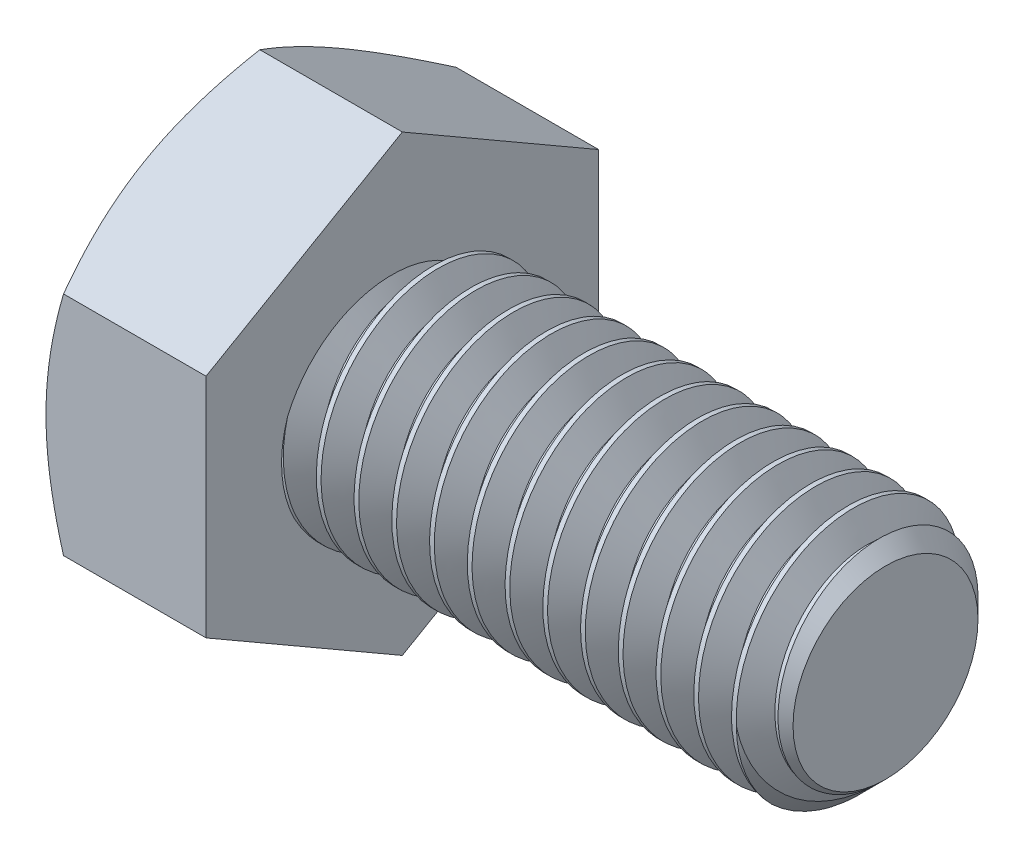
SolidWorks part; units mm, degrees
ref_plane "Front Plane" through (0, 0, 0) normal (0, 0, 1) x (1, 0, 0)
ref_plane "Top Plane" through (0, 0, 0) normal (0, 1, 0) x (1, 0, 0)
ref_plane "Right Plane" through (0, 0, 0) normal (1, 0, 0) x (0, 0, -1)
sketch "Sketch1" plane through (0, 0, 0) normal (0, 0, 1) x (1, 0, 0)
  line L0 (-10.65, 0) -> (10.65, 0) construction
  line L1 (-5.35, 6.5) -> (-5.35, -6.5) construction
  line L2 (-10.65, 6.5) -> (-10.65, -6.5) construction
  line L3 (10.65, 4) -> (10.65, -4) construction
  point P8 (6.275, -4)
  dimension "D1" = 4.375
  dimension "Thread Dia" = 8
  dimension "Hex" = 13
  dimension "Head Ht" = 5.3
  dimension "Length" = 16
ref_plane "Plane2" through (10.65, 0, 0) normal (1, 0, 0) x (0, 0, -1)
sketch "Sketch2" plane through (10.65, 0, 0) normal (1, 0, 0) x (0, 0, -1)
  circle A0 centre (0, 0) radius 4
extrude "Boss-Extrude1" add sketch "Sketch2" against normal up to vertex (16 mm away) up to point (-5.35, -6.5, 0)
sketch "Sketch4" plane through (10.65, 0, 0) normal (1, 0, 0) x (0, 0, -1)
  circle A1 centre (0, 0) radius 4
  circle A2 centre (0, 0) radius 4
  dimension "D1" = 0
curve "Helix/Spiral1" pitch 1.25 height 17.25 turns 13.8 parameters "Pitch"=1.25
chamfer "Chamfer1" distance 0.9375 angle 45 1 edges at (10.65, 0, -4)
sketch "Sketch5" plane through (0, 0, 0) normal (0, 0, 1) x (1, 0, 0)
  line L0 (10.65, 4) -> (11.1187, 3.1881)
  line L1 (11.1187, 3.1881) -> (11.275, 3.1881)
  line L2 (11.275, 3.1881) -> (11.7437, 4)
  line L3 (10.65, 4) -> (11.7437, 4)
  line L4 (11.1969, 3.1881) -> (11.1969, 4) construction
  line L5 (10.8844, 3.5941) -> (11.5094, 3.5941) construction
  line L6 (10.65, -4) -> (10.65, 4) construction
  dimension "D1" = 60
  dimension "D2" = 0.1562
  dimension "D3" = 0.625
sweep "Cut-Sweep1" cut profiles "Sketch5" path "Helix/Spiral1" align with end faces yes
sketch "Sketch3" plane through (-5.35, 0, 0) normal (-1, 0, 0) x (0, 0, 1)
  line L0 (0, 6.5) -> (0, -6.5) construction
  line L1 (-6.5, -3.7528) -> (0, -7.5056)
  line L2 (0, -7.5056) -> (6.5, -3.7528)
  line L3 (6.5, -3.7528) -> (6.5, 3.7528)
  line L4 (6.5, 3.7528) -> (0, 7.5056)
  line L5 (0, 7.5056) -> (-6.5, 3.7528)
  line L6 (-6.5, 3.7528) -> (-6.5, -3.7528)
  circle A0 centre (0, 0) radius 6.5 construction
extrude "Boss-Extrude2" add sketch "Sketch3" along normal up to vertex (5.3 mm away) up to point (-10.65, -6.5, 0)
sketch "Sketch6" plane through (-10.65, 0, 0) normal (-1, 0, 0) x (0, 0, 1)
  circle A0 centre (0, 0) radius 6.5 construction
  circle A1 centre (0, 0) radius 6.5
extrude "Cut-Extrude1" cut sketch "Sketch6" against normal through all draft 60 flip side to cut
sketch "Sketch7" plane through (-10.65, 0, 0) normal (-1, 0, 0) x (0, 0, 1)
  line L0 (0, 0) -> (0, 6.5) construction
  line L2 (0, 6.5) -> (0, -6.5) construction
  line L3 (-5.6292, 3.25) -> (5.6292, 3.25) construction
  circle A1 centre (0, 0) radius 6.5 construction
  text T0 "8.8\r\n" font "Arial" height in points 6
  point P8 (0, 3.25)
extrude "Cut-Extrude2" cut sketch "Sketch7" against normal blind 0.25
sketch "Sketch9" plane through (0, 0, 0) normal (0, 0, 1) x (1, 0, 0)
  line L0 (-5.35, 4) -> (-5.35, 0)
  line L1 (-5.35, 0) -> (-39.35, 0)
  line L2 (-39.35, 0) -> (-43.35, 4)
  line L3 (-43.35, 4) -> (-5.35, 4)
  line L4 (-10.65, 0) -> (10.65, 0) construction
  line L5 (-5.35, 6.5) -> (-5.35, -6.5) construction
  line L6 (10.65, 4) -> (10.65, -4) construction
  dimension "D1" = 45
  dimension "MinThreadLg" = 54
revolve "Revolve1" [suppressed] add sketch "Sketch9" angle 360 about L1
equation "\"D2@Sketch5\" = \"Pitch@Helix/Spiral1\"*.125"
equation "\"D3@Sketch5\" = \"Pitch@Helix/Spiral1\"*.50"
equation "\"D3@Helix/Spiral1\" = \"Length@Sketch1\"+\"Pitch@Helix/Spiral1\""
equation "\"D1@Chamfer1\" = \"Pitch@Helix/Spiral1\"*.750"
equation "\"D1@Sketch1\" = \"Pitch@Helix/Spiral1\"*3.50"
